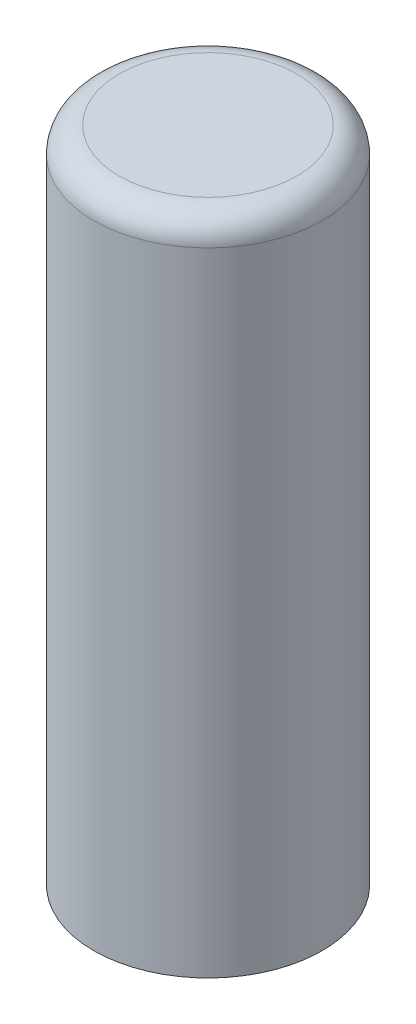
SolidWorks part; units mm, degrees
ref_plane "Front Plane" through (0, 0, 0) normal (0, 0, 1) x (1, 0, 0)
ref_plane "Top Plane" through (0, 0, 0) normal (0, 1, 0) x (1, 0, 0)
ref_plane "Right Plane" through (0, 0, 0) normal (1, 0, 0) x (0, 0, -1)
sketch "Sketch1" plane through (0, 0, 0) normal (0, 1, 0) x (1, 0, 0)
  line L0 (8.375, -6.9643) -> (9.075, -6.9643)
  line L1 (-8.725, -6.9643) -> (-8.375, -6.9643)
  line L2 (-8.725, -6.9643) -> (-8.725, -8.6143)
  line L3 (-8.725, -8.6143) -> (-8.375, -8.6143)
  line L4 (9.075, -6.9643) -> (9.075, -8.6143)
  line L6 (-8.375, -6.9643) -> (-8.375, -6.2043)
  line L12 (8.375, -6.9643) -> (8.375, -6.2043)
  line L14 (-8.375, -6.2043) -> (-8.375, 9.6457)
  line L16 (8.375, -6.2043) -> (8.375, 9.6457)
  line L19 (-5, 13.0207) -> (5, 13.0207)
  line L22 (-8.375, -8.6143) -> (-8.375, -9.6109)
  line L24 (8.375, -8.6143) -> (8.375, -9.6109)
  line L25 (8.375, -8.6143) -> (9.075, -8.6143)
  circle A0 centre (0, 0) radius 15.5912
  arc A1 (-5, 13.0207) -> (-8.375, 9.6457) centre (-5, 9.6457) ccw
  arc A2 (8.375, 9.6457) -> (5, 13.0207) centre (5, 9.6457) ccw
  arc A4 (-8.375, -9.6109) -> (8.375, -9.6109) centre (0, 0) ccw
  dimension "D5" = 16.75
  dimension "D6" = 0.76
  dimension "D1" = 17.8
  dimension "D2" = 1.65
  dimension "D3" = 15.85
  dimension "D4" = 10
  dimension "D8" = 0.35
  dimension "D9" = 0.7
extrude "Boss-Extrude1" add sketch "Sketch1" along normal blind 71
sketch "Sketch2" plane through (0, 0, 0) normal (0, -1, 0) x (1, 0, 0)
  line L1 (-8.725, 8.6143) -> (9.075, 8.6143)
  line L2 (-8.725, 8.6143) -> (-8.725, 6.9643)
  line L3 (-8.725, 6.9643) -> (9.075, 6.9643)
  line L4 (9.075, 8.6143) -> (9.075, 6.9643)
  circle A0 centre (0, 0) radius 15.5912
extrude "Boss-Extrude2" add sketch "Sketch2" along normal blind 1.25
sketch "Sketch3" plane through (0, -1.25, 0) normal (0, -1, 0) x (1, 0, 0)
  circle A0 centre (0, 0) radius 15.5912
extrude "Boss-Extrude3" add sketch "Sketch3" along normal blind 4
sketch "Sketch16" plane through (0, 0, 0) normal (0, 1, 0) x (1, 0, 0)
  line L0 (-3, -9.9011) -> (0, -9.9011)
  line L1 (0, -9.9011) -> (3, -9.9011)
  line L2 (3, -9.9011) -> (6, -9.9011)
  line L3 (-3, -9.9011) -> (-6, -9.9011)
  line L5 (-1.4599, -11.5773) -> (1.5401, -11.5773)
  line L6 (1.5401, -11.5773) -> (4.5401, -11.5773)
  circle A0 centre (0, -9.9011) radius 0.75
  circle A1 centre (3, -9.9011) radius 0.75
  circle A2 centre (-3, -9.9011) radius 0.75
  circle A3 centre (-6, -9.9011) radius 0.75
  circle A4 centre (6, -9.9011) radius 0.75
  circle A6 centre (1.5401, -11.5773) radius 0.75
  arc A9 (5.2892, -11.5989) -> (4.0065, -12.102) centre (4.5396, -11.5745) ccw
  arc A10 (-3.9429, -12.1229) -> (-5.2052, -11.6369) centre (-4.4576, -11.5773) ccw
  circle A11 centre (-1.4576, -11.5771) radius 0.75
  arc A12 (4.0065, -12.102) -> (5.2892, -11.5989) centre (0, 0) ccw
  arc A13 (-5.2052, -11.6369) -> (-3.9429, -12.1229) centre (0, 0) ccw
  dimension "D1" = 1.5
  dimension "D2" = 3
  dimension "D3" = 1.5
  dimension "D4" = 3
extrude "Cut-Extrude4" cut sketch "Sketch16" against normal blind 11.5 contours A4 | L2 A1 L1 | L1 A1 L2 | L1 A0 L0 | L0 A0 L1 | L0 A2 L3 | L3 A2 L0 | A3 | A6 | A0 | A9 A12 | A11 | A10 A13 region at (-3, 0, 9.5828) region at (-3, 0, 10.2194) region at (6, 0, 9.1723) region at (3, 0, 9.5828) region at (3, 0, 10.2194) region at (0, 0, 9.5828) region at (0, 0, 10.2194) region at (-6.7288, 0, 9.9011)
sketch "Sketch18" plane through (0, -5.25, 0) normal (0, -1, 0) x (1, 0, 0)
  circle A0 centre (0, 0) radius 15.5912
  circle A1 centre (0, 0) radius 13.0957
extrude "Boss-Extrude8" add sketch "Sketch18" along normal blind 10
fillet "Fillet3" radius 7 1 edges at (0, -5.25, -13.0957)
sketch "Sketch26" plane through (0, 71, 0) normal (0, 1, 0) x (1, 0, 0)
  circle A0 centre (0, 0) radius 15.5912
extrude "Boss-Extrude9" add sketch "Sketch26" along normal blind 3.5
fillet "Fillet4" radius 3.5 1 edges at (0, 74.5, 15.5912)
